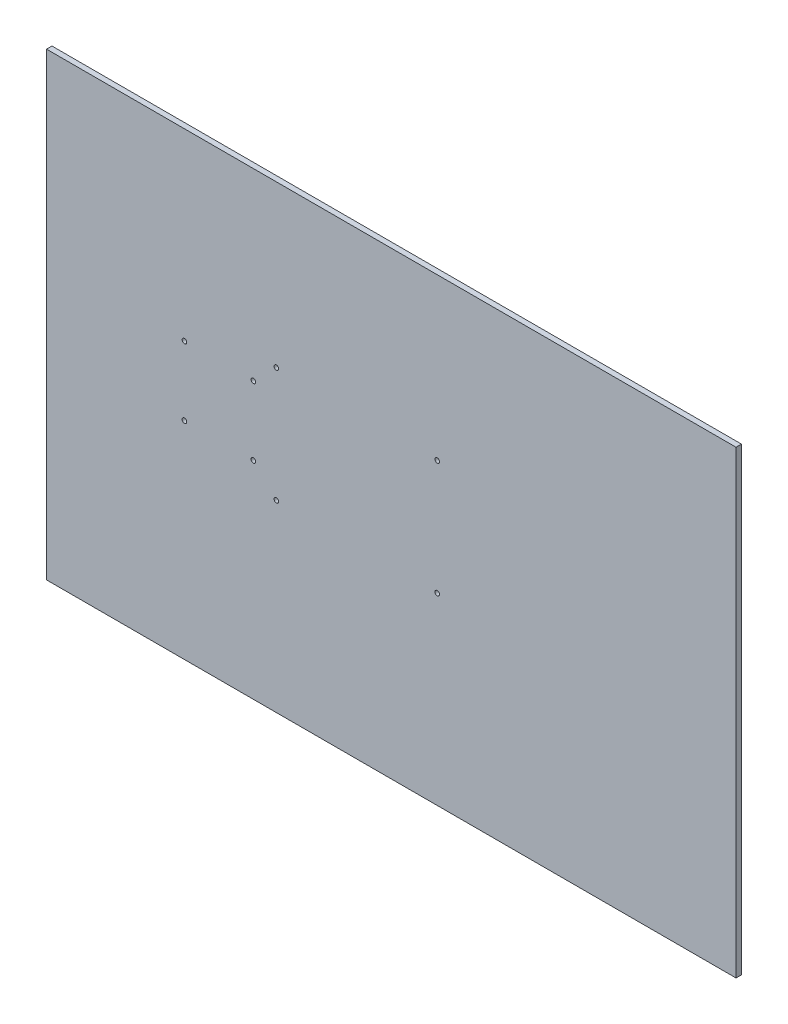
SolidWorks part; units mm, degrees
ref_plane "Front Plane" through (0, 0, 0) normal (0, 0, 1) x (1, 0, 0)
ref_plane "Top Plane" through (0, 0, 0) normal (0, 1, 0) x (1, 0, 0)
ref_plane "Right Plane" through (0, 0, 0) normal (1, 0, 0) x (0, 0, -1)
sketch "Sketch2" plane through (0, 0, 0) normal (0, 0, 1) x (1, 0, 0)
  line L0 (0, 254) -> (0, -254) construction
  line L1 (-381, -254) -> (381, -254)
  line L2 (-381, -254) -> (-381, 254)
  line L3 (-381, 254) -> (381, 254)
  line L4 (381, -254) -> (381, 254)
  line L5 (-381, -254) -> (381, 254) construction
  line L6 (-381, 254) -> (381, -254) construction
  line L7 (-304.8, 254) -> (-304.8, -254) construction
  line L8 (-355.6, 254) -> (-355.6, -254) construction
  line L9 (-330.2, 254) -> (-330.2, -254) construction
  line L10 (-279.4, 254) -> (-279.4, -254) construction
  line L11 (-254, 254) -> (-254, -254) construction
  line L12 (-228.6, 254) -> (-228.6, -254) construction
  line L13 (-203.2, 254) -> (-203.2, -254) construction
  line L14 (-177.8, 254) -> (-177.8, -254) construction
  line L15 (-152.4, 254) -> (-152.4, -254) construction
  line L16 (-127, 254) -> (-127, -254) construction
  line L17 (-101.6, 254) -> (-101.6, -254) construction
  line L18 (-76.2, 254) -> (-76.2, -254) construction
  line L19 (-50.8, 254) -> (-50.8, -254) construction
  line L20 (-25.4, 254) -> (-25.4, -254) construction
  line L21 (25.4, 254) -> (25.4, -254) construction
  line L22 (50.8, 254) -> (50.8, -254) construction
  line L23 (76.2, 254) -> (76.2, -254) construction
  line L24 (101.6, 254) -> (101.6, -254) construction
  line L25 (127, 254) -> (127, -254) construction
  line L26 (152.4, 254) -> (152.4, -254) construction
  line L27 (177.8, 254) -> (177.8, -254) construction
  line L28 (203.2, 254) -> (203.2, -254) construction
  line L29 (228.6, 254) -> (228.6, -254) construction
  line L30 (254, 254) -> (254, -254) construction
  line L31 (279.4, 254) -> (279.4, -254) construction
  line L32 (304.8, 254) -> (304.8, -254) construction
  line L33 (330.2, 254) -> (330.2, -254) construction
  line L34 (355.6, 254) -> (355.6, -254) construction
  line L35 (-381, 0) -> (381, 0) construction
  line L36 (-381, 152.4) -> (381, 152.4) construction
  line L37 (-381, 177.8) -> (381, 177.8) construction
  line L38 (-381, 203.2) -> (381, 203.2) construction
  line L39 (-381, 228.6) -> (381, 228.6) construction
  line L40 (-381, 127) -> (381, 127) construction
  line L41 (-381, 101.6) -> (381, 101.6) construction
  line L42 (-381, 76.2) -> (381, 76.2) construction
  line L43 (-381, 50.8) -> (381, 50.8) construction
  line L44 (-381, 25.4) -> (381, 25.4) construction
  line L45 (-381, -25.4) -> (381, -25.4) construction
  line L46 (-381, -50.8) -> (381, -50.8) construction
  line L47 (-381, -76.2) -> (381, -76.2) construction
  line L48 (-381, -101.6) -> (381, -101.6) construction
  line L49 (-381, -127) -> (381, -127) construction
  line L50 (-381, -152.4) -> (381, -152.4) construction
  line L51 (-381, -177.8) -> (381, -177.8) construction
  line L52 (-381, -203.2) -> (381, -203.2) construction
  line L53 (-381, -228.6) -> (381, -228.6) construction
  line L54 (-381, 12.7) -> (381, 12.7) construction
  circle A0 centre (-228.6, 50.8) radius 2.555
  circle A1 centre (-228.6, -25.4) radius 2.555
  circle A2 centre (-152.4, 50.8) radius 2.555
  circle A3 centre (-152.4, -25.4) radius 2.555
  circle A5 centre (-127, 76.2) radius 2.555
  circle A6 centre (-127, -50.8) radius 2.555
  circle A9 centre (50.8, 76.2) radius 2.555
  circle A10 centre (50.8, -50.8) radius 2.555
  point P0 (0, 0)
  point P120 (-127, -50.8)
  point P121 (50.8, -50.8)
  point P122 (50.8, 76.2)
  point P123 (-127, 76.2)
  dimension "D17" = 5.11
  dimension "D18" = 5.11
  dimension "D19" = 5.11
  dimension "D20" = 5.11
  dimension "D22" = 5.11
  dimension "D23" = 5.11
  dimension "D24" = 5.11
  dimension "D25" = 5.11
  dimension "D1" = 762
  dimension "D2" = 508
  dimension "D3" = 25.4
  dimension "D4" = 25.4
  dimension "D5" = 25.4
  dimension "D6" = 25.4
  dimension "D7" = 25.4
  dimension "D8" = 25.4
  dimension "D9" = 25.4
  dimension "D10" = 25.4
  dimension "D11" = 25.4
  dimension "D12" = 25.4
  dimension "D13" = 25.4
  dimension "D14" = 25.4
  dimension "D15" = 25.4
  dimension "D16" = 25.4
  dimension "D21" = 12.7
extrude "Boss-Extrude1" add sketch "Sketch2" along normal blind 6
